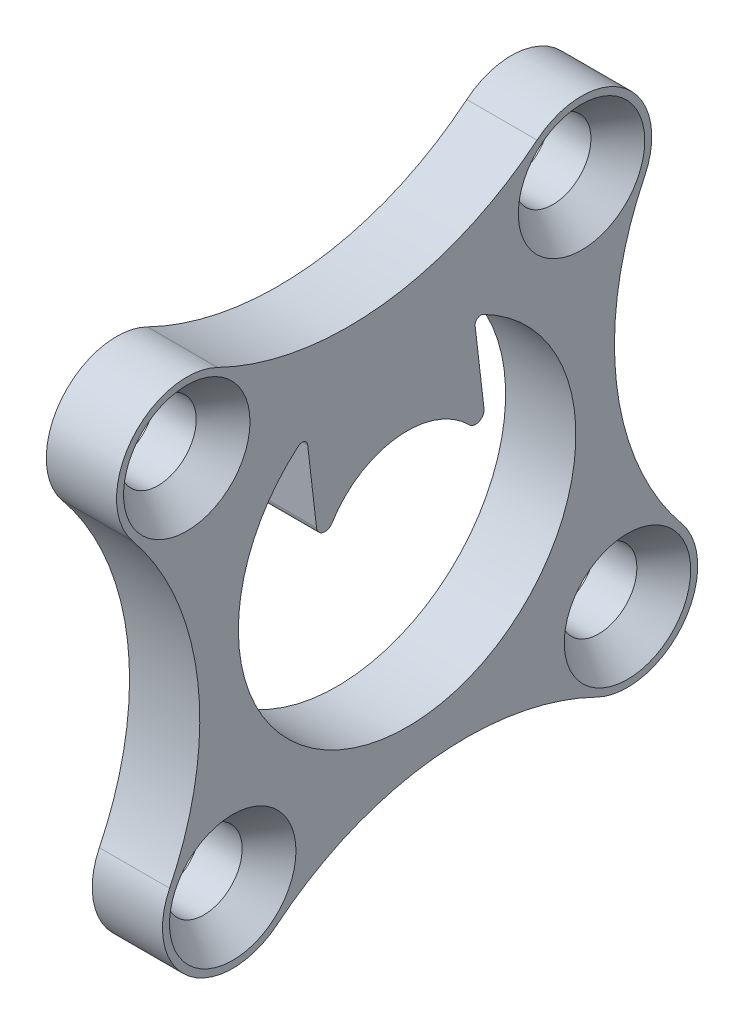
SolidWorks part; units mm, degrees
material "6061-T6 (SS)"
ref_plane "Front Plane" through (0, 0, 0) normal (0, 0, 1) x (1, 0, 0)
ref_plane "Top Plane" through (0, 0, 0) normal (0, 1, 0) x (1, 0, 0)
ref_plane "Right Plane" through (0, 0, 0) normal (1, 0, 0) x (0, 0, -1)
sketch "Sketch1" plane through (-42.315, 0, 0) normal (-1, 0, 0) x (0, 0, 1)
  line L0 (4.4956, 5.6702) -> (4.0938, 2.2179)
  line L1 (4.6911, 7.3501) -> (4.4779, 5.5184) construction
  line L2 (-3.4751, 3.0987) -> (-3.0733, 6.551)
  line L3 (-2.8778, 8.231) -> (-3.4541, 3.2788) construction
  line L5 (4.4779, 5.5184) -> (3.9129, 0.6634) construction
  line L6 (7.882, -9.9581) -> (-7.882, 9.9581) construction
  line L7 (-9.9581, -7.882) -> (9.9581, 7.882) construction
  arc A0 (4.0938, 2.2179) -> (3.3899, 2.0638) centre (3.7154, 2.2619) cw
  arc A1 (3.3899, 2.0638) -> (-2.8254, 2.7871) centre (0, 0) ccw
  arc A2 (-2.8254, 2.7871) -> (-3.4751, 3.0987) centre (-3.0966, 3.0547) cw
  circle A3 centre (0, 0) radius 3.9687 construction
  circle A4 centre (0, 0) radius 3.9687 construction
  arc A5 (4.4956, 5.6702) -> (4.9114, 5.8351) centre (4.7479, 5.6408) cw
  arc A8 (4.9114, 5.8351) -> (-3.4402, 6.8071) centre (0, 0) cw
  arc A9 (-3.4402, 6.8071) -> (-3.0733, 6.551) centre (-3.3256, 6.5804) cw
  circle A10 centre (0, 0) radius 15.875
  arc A11 (-3.4605, 6.6539) -> (4.896, 5.6814) centre (0, 0) ccw construction
  circle A12 centre (9.9581, 7.882) radius 3.175 construction
  circle A13 centre (9.9581, 7.882) radius 2.6924 construction
  circle A14 centre (0, 0) radius 9.525 construction
  dimension "D1" = 0.381
  dimension "D2" = 0.254
  dimension "D3" = 25.4
  dimension "D4" = 0.127
  dimension "D6" = 5.3848
  dimension "D7" = 19.05
  dimension "D5" = 45
extrude "Boss-Extrude1" add sketch "Sketch1" against normal blind 3.175
sketch "Sketch2" plane through (-42.315, 0, 0) normal (-1, 0, 0) x (0, 0, 1)
  line L0 (-9.9581, -7.882) -> (9.9581, 7.882) construction
  line L1 (4.4956, 5.6702) -> (4.0938, 2.2179) construction
  line L2 (9.4611, -1.1011) -> (15.7686, -1.8351)
  arc A0 (12.4477, 9.8525) -> (15.7686, -1.8351) centre (0, 0) cw
  circle A1 centre (0, 0) radius 15.875 construction
  circle A3 centre (0, 0) radius 9.525 construction
  arc A5 (12.4155, 5.8715) -> (12.4477, 9.8525) centre (9.9581, 7.882) ccw
  circle A6 centre (9.9581, 7.882) radius 3.175 construction
  arc A7 (12.4155, 5.8715) -> (9.4611, -1.1011) centre (22.8412, -2.6582) ccw
extrude "Cut-Extrude1" cut sketch "Sketch2" against normal through all
mirror "Mirror1" about plane through (-39.14, -1.1011, 9.4611) normal (0, -0.9933, -0.1156) of "Cut-Extrude1"
pattern_circular "CirPattern2" count 4 over 360 about axis through (-42.315, 0, 0) along (-1, 0, 0) of "Cut-Extrude1", "Mirror1"
hole_wizard "CSK for #4 Flat Head Machine Screw1" positions "Sketch3" profile "Sketch4" countersink size "#4" standard "ANSI Inch" end condition up to next
sketch "Sketch3" plane through (-39.14, 0, 0) normal (1, 0, 0) x (0, 0, -1)
  point P0 (7.882, 9.9581)
  point P3 (7.882, 9.9581)
  point P6 (7.882, 9.9581)
  point P9 (7.882, 9.9581)
  point P13 (-9.9581, 7.882)
  point P16 (-7.882, -9.9581)
  point P19 (9.9581, -7.882)
sketch "Sketch4" plane through (-39.14, 9.9581, -7.882) normal (0, 1, 0) x (0, 0, -1)
  line L0 (0, 0) -> (0, 3.175)
  line L1 (0, 3.175) -> (1.7272, 3.175)
  line L2 (1.7272, 3.175) -> (1.7272, 1.3003)
  line L3 (1.7272, 1.3003) -> (2.8575, 0)
  line L5 (2.8575, 0) -> (0, 0)
  line L6 (-1.7272, 1.3003) -> (-2.8575, 0) construction
  line L11 (0, -6.35) -> (0, 107.95) construction
  dimension "Thru Hole Dia." = 3.4544
  dimension "Thru Hole Depth" = 3.175
  dimension "Near C'Sink Dia." = 5.715
  dimension "Near C'Sink Angle" = 82
